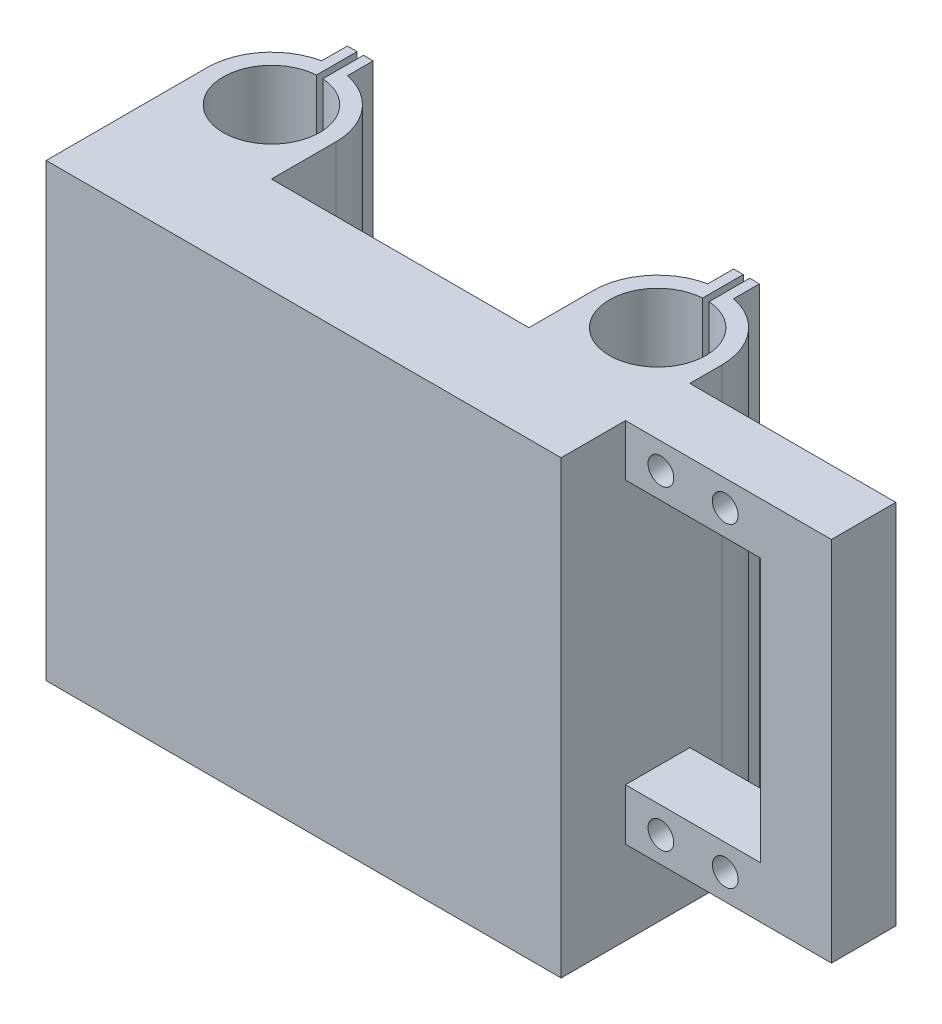
SolidWorks part; units mm, degrees
ref_plane "Alzado" through (0, 0, 0) normal (0, 0, 1) x (1, 0, 0)
ref_plane "Planta" through (0, 0, 0) normal (0, 1, 0) x (1, 0, 0)
ref_plane "Vista lateral" through (0, 0, 0) normal (1, 0, 0) x (0, 0, -1)
sketch "Croquis1" plane through (0, 0, 0) normal (0, 1, 0) x (1, 0, 0)
  line L0 (-58.0166, 0) -> (58.0166, 0) construction
  line L5 (40, -25) -> (40, 0)
  line L6 (11.3137, 4) -> (20.8348, 4)
  line L7 (0, 33.1459) -> (0, -45.5761) construction
  line L8 (-40, -25) -> (-40, 0)
  line L9 (-11.3137, 4) -> (-20.8348, 4)
  line L10 (-40, -25) -> (40, -25)
  arc A1 (11.3137, 4) -> (-11.3137, 4) centre (0, 0) ccw
  arc A2 (40, 0) -> (20.8348, 4) centre (30, 0) ccw
  arc A3 (-40, 0) -> (-20.8348, 4) centre (-30, 0) cw
  point P3 (0, 0)
  dimension "D1" = 20
  dimension "D2" = 24
  dimension "D3" = 30
  dimension "D4" = 4
  dimension "D5" = 25
extrude "Saliente-Extruir1" add sketch "Croquis1" along normal blind 70
sketch "Croquis3" plane through (0, 70, 0) normal (0, 1, 0) x (1, 0, 0)
  line L0 (-30, 0) -> (-30, 16.5211) construction
  line L1 (-32, 9.798) -> (-32, 13.798)
  line L2 (-32, 13.798) -> (-28, 13.798)
  line L3 (-28, 9.798) -> (-28, 13.798)
  line L4 (0, -55) -> (0, 55) construction
  line L5 (28, 9.798) -> (28, 13.798)
  line L6 (32, 13.798) -> (28, 13.798)
  line L7 (32, 9.798) -> (32, 13.798)
  arc A0 (-20.8348, 4) -> (-40, 0) centre (-30, 0) ccw construction
  arc A1 (-28, 9.798) -> (-32, 9.798) centre (-30, 0) ccw
  arc A2 (28, 9.798) -> (32, 9.798) centre (30, 0) cw
  point P10 (-30, 13.798)
  dimension "D1" = 4
  dimension "D2" = 4
extrude "Saliente-Extruir2" add sketch "Croquis3" against normal up to surface (70 mm away) up to face at (0, 0, 1.3027)
sketch "Croquis4" plane through (0, 70, 0) normal (0, 1, 0) x (1, 0, 0)
  line L0 (-30.5, 7.4833) -> (-30.5, 14.6548)
  line L1 (-30, 0) -> (-30, 16.6168) construction
  line L2 (-30.5, 14.6548) -> (-29.5, 14.6548)
  line L3 (-29.5, 7.4833) -> (-29.5, 14.6548)
  line L4 (0, -55) -> (0, 55) construction
  line L5 (29.5, 7.4833) -> (29.5, 14.6548)
  line L6 (30.5, 14.6548) -> (29.5, 14.6548)
  line L7 (30.5, 7.4833) -> (30.5, 14.6548)
  arc A1 (-30.5, 7.4833) -> (-29.5, 7.4833) centre (-30, 0) ccw
  arc A2 (30.5, 7.4833) -> (29.5, 7.4833) centre (30, 0) cw
  point P8 (-30, 14.6548)
  point P16 (30, 14.6548)
  dimension "D1" = 15
  dimension "D2" = 1
extrude "Cortar-Extruir2" cut sketch "Croquis4" against normal through all both and the other way through all
sketch "Croquis5" plane through (0, 70, 0) normal (0, 1, 0) x (1, 0, 0)
  line L0 (-20, 0) -> (-20, -10)
  line L1 (-20, -10) -> (20, -10)
  line L2 (0, 31.6012) -> (0, -31.6012) construction
  line L3 (-20, -10) -> (-30, -10) construction
  line L7 (20, 0) -> (20, -10)
  line L8 (-20.8348, 4) -> (-20.8348, 13.996)
  line L9 (-20.8348, 13.996) -> (20.8348, 13.996)
  line L10 (20.8348, 13.996) -> (20.8348, 4)
  arc A0 (11.3137, 4) -> (-11.3137, 4) centre (0, 0) ccw construction
  arc A3 (-32, 9.798) -> (-40, 0) centre (-30, 0) ccw construction
  arc A4 (-32, 9.798) -> (-40, 0) centre (-30, 0) ccw construction
  arc A5 (-20, 0) -> (-20.8348, 4) centre (-30, 0) ccw
  arc A6 (-32, 9.798) -> (-40, 0) centre (-30, 0) ccw construction
  arc A7 (20, 0) -> (20.8348, 4) centre (30, 0) cw
  point P9 (0, 0)
  point P16 (0, -10)
extrude "Cortar-Extruir3" cut sketch "Croquis5" against normal blind 30
sketch "Croquis9" plane through (0, 0, 0) normal (0, 1, 0) x (1, 0, 0)
  line L0 (-20, 0) -> (-20, -10)
  line L1 (-20, -10) -> (20, -10)
  line L2 (0, 31.6012) -> (0, -31.6012) construction
  line L3 (-20, -10) -> (-30, -10) construction
  line L7 (20, 0) -> (20, -10)
  line L8 (-20.8348, 4) -> (-20.8348, 13.996)
  line L9 (-20.8348, 13.996) -> (20.8348, 13.996)
  line L10 (20.8348, 13.996) -> (20.8348, 4)
  arc A4 (-32, 9.798) -> (-40, 0) centre (-30, 0) ccw construction
  arc A5 (-20, 0) -> (-20.8348, 4) centre (-30, 0) ccw
  arc A6 (-32, 9.798) -> (-40, 0) centre (-30, 0) ccw construction
  arc A7 (20, 0) -> (20.8348, 4) centre (30, 0) cw
  point P16 (0, -10)
extrude "Cortar-Extruir6" cut sketch "Croquis9" along normal blind 30 contours L9 L10 A7 L7 L1 L0 A5 L8
sketch "Croquis6" plane through (0, 70, 0) normal (0, 1, 0) x (1, 0, 0)
  line L0 (0, 0) -> (-12.9386, 12.9386) construction
  line L1 (0, 0) -> (0, 16.0434) construction
  circle A0 centre (0, 0) radius 5
  circle A1 centre (-6.0104, 6.0104) radius 1.6
  circle A2 centre (6.0104, 6.0104) radius 1.6
  circle A3 centre (6.0104, -6.0104) radius 1.6
  circle A4 centre (-6.0104, -6.0104) radius 1.6
  point P16 (0, 0)
  dimension "D1" = 10
  dimension "D3" = 3.2
  dimension "D4" = 8.5
  dimension "D2" = 45
  dimension "D5" = 4
extrude "Cortar-Extruir4" cut sketch "Croquis6" against normal through all both and the other way through all
sketch "Croquis7" plane through (40, 0, 0) normal (1, 0, 0) x (0, 0, -1)
  line L0 (-15, 70) -> (-15, 62)
  line L1 (-25, 70) -> (0, 70) construction
  line L2 (-15, 62) -> (-5, 62)
  line L3 (-35.4515, 41.5) -> (26.4894, 41.5) construction
  line L4 (-5, 62) -> (-5, 70)
  line L5 (-5, 70) -> (-15, 70)
  line L6 (-25, 70) -> (-25, 0) construction
  line L7 (-5, 13) -> (-15, 13)
  line L8 (-5, 21) -> (-5, 13)
  line L9 (-15, 21) -> (-5, 21)
  line L10 (-15, 13) -> (-15, 21)
  dimension "D1" = 8
  dimension "D2" = 20.5
  dimension "D3" = 10
  dimension "D4" = 10
extrude "Saliente-Extruir3" add sketch "Croquis7" along normal blind 32
sketch "Croquis8" plane through (0, 0, 15) normal (0, 0, 1) x (1, 0, 0)
  line L0 (50.5, 62) -> (50.5, 21) construction
  line L1 (72, 62) -> (40, 62) construction
  line L2 (49.485, 41.5) -> (51.515, 41.5) construction
  line L3 (72, 21) -> (40, 21) construction
  line L7 (40, 70) -> (40, 0) construction
  circle A0 centre (45.5, 66) radius 2
  circle A1 centre (55.5, 66) radius 2
  circle A2 centre (45.5, 17) radius 2
  circle A3 centre (55.5, 17) radius 2
  point P9 (50.5, 41.5)
  dimension "D1" = 10
  dimension "D2" = 4
  dimension "D3" = 5.5
  dimension "D4" = 49
extrude "Cortar-Extruir5" cut sketch "Croquis8" against normal through all both and the other way through all
sketch "Croquis10" plane through (0, 62, 0) normal (0, -1, 0) x (1, 0, 0)
  line L0 (61, 5) -> (61, 15)
  line L1 (72, 5) -> (40, 5) construction
  line L2 (72, 15) -> (40, 15) construction
  line L3 (61, 15) -> (72, 15)
  line L4 (72, 15) -> (72, 5) construction
  line L5 (72, 15) -> (72, 5)
  line L6 (72, 5) -> (61, 5)
  dimension "D1" = 11
extrude "Saliente-Extruir4" add sketch "Croquis10" along normal up to next
